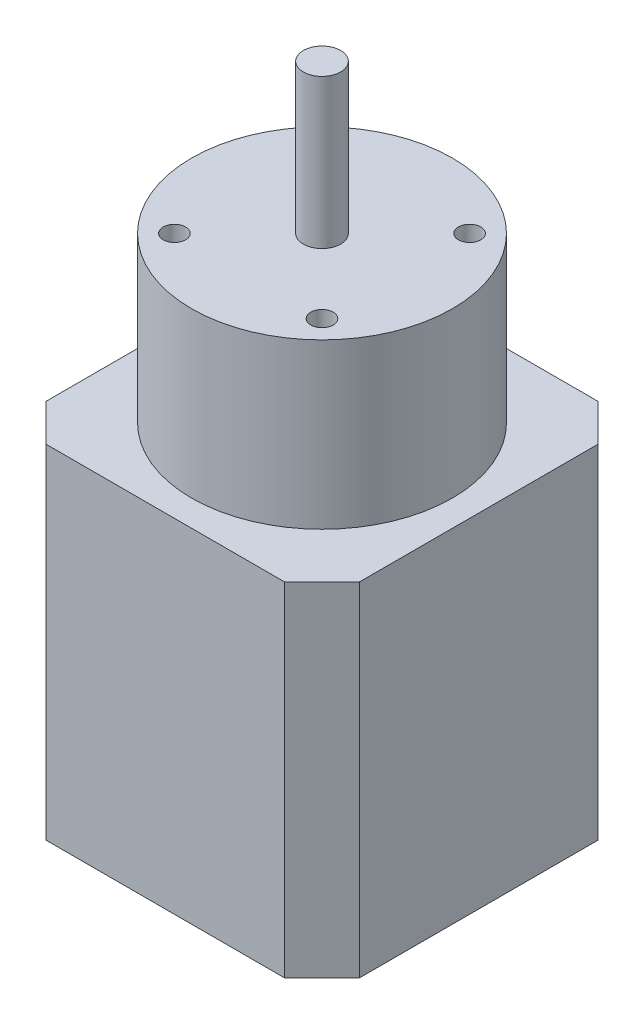
SolidWorks part; units mm, degrees
ref_plane "Front Plane" through (0, 0, 0) normal (0, 0, 1) x (1, 0, 0)
ref_plane "Top Plane" through (0, 0, 0) normal (0, 1, 0) x (1, 0, 0)
ref_plane "Right Plane" through (0, 0, 0) normal (1, 0, 0) x (0, 0, -1)
sketch "Sketch1" plane through (0, 0, 0) normal (0, 1, 0) x (1, 0, 0)
  line L1 (-21, -21) -> (21, -21)
  line L2 (-21, -21) -> (-21, 21)
  line L3 (-21, 21) -> (21, 21)
  line L4 (21, -21) -> (21, 21)
  line L5 (-21, -21) -> (21, 21) construction
  line L6 (-21, 21) -> (21, -21) construction
  point P0 (0, 0)
  dimension "D1" = 42
  dimension "D2" = 42
extrude "Boss-Extrude1" add sketch "Sketch1" along normal blind 46
chamfer "Chamfer1" distance 5 angle 45 4 edges at (-21, 23, -21) (21, 23, -21) (21, 23, 21) (-21, 23, 21)
sketch "Sketch5" plane through (0, 46, 0) normal (0, 1, 0) x (1, 0, 0)
  circle A0 centre (0, 0) radius 17.5
  dimension "D1" = 35
extrude "Boss-Extrude4" add sketch "Sketch5" along normal blind 22
sketch "Sketch6" plane through (0, 68, 0) normal (0, 1, 0) x (1, 0, 0)
  circle A0 centre (0, 0) radius 2.5
  dimension "D1" = 5
extrude "Boss-Extrude5" add sketch "Sketch6" along normal blind 20
sketch "Sketch7" plane through (0, 68, 0) normal (0, 1, 0) x (1, 0, 0)
  line L0 (-9.8995, -9.8995) -> (-9.8995, 9.8995) construction
  line L1 (-9.8995, 9.8995) -> (9.8995, 9.8995) construction
  circle A0 centre (0, 0) radius 14 construction
  circle A1 centre (-9.8995, 9.8995) radius 1.5
  circle A2 centre (9.8995, 9.8995) radius 1.5
  circle A3 centre (9.8995, -9.8995) radius 1.5
  circle A4 centre (-9.8995, -9.8995) radius 1.5
  dimension "D1" = 3
  dimension "D2" = 28
extrude "Cut-Extrude2" cut sketch "Sketch7" against normal blind 5
